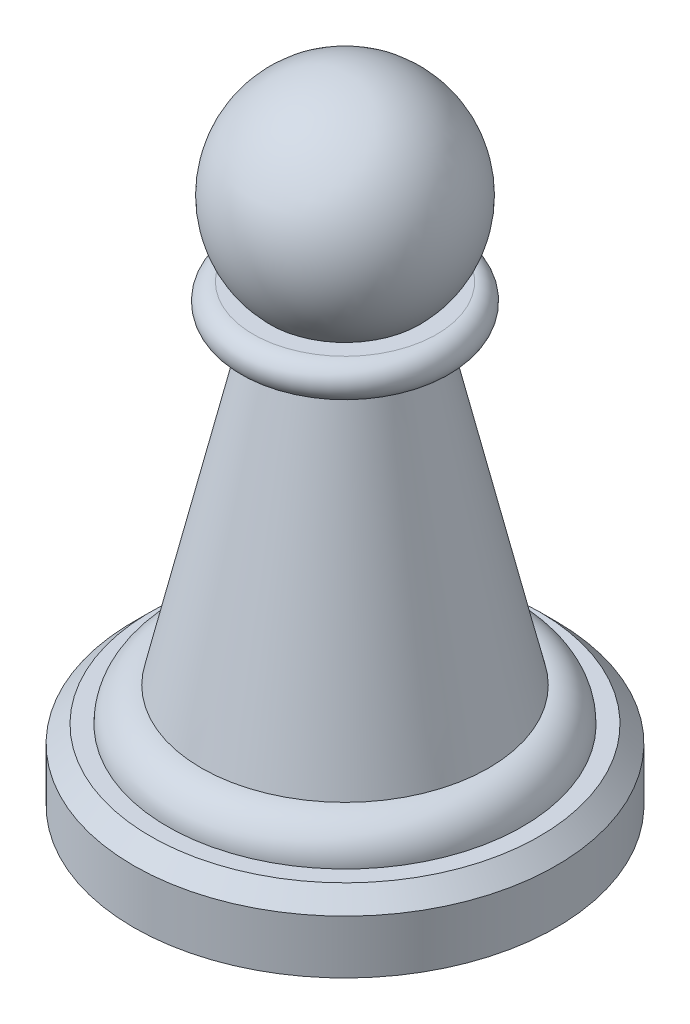
SolidWorks part; units mm, degrees
ref_plane "Front Plane" through (0, 0, 0) normal (0, 0, 1) x (1, 0, 0)
ref_plane "Top Plane" through (0, 0, 0) normal (0, 1, 0) x (1, 0, 0)
ref_plane "Right Plane" through (0, 0, 0) normal (1, 0, 0) x (0, 0, -1)
sketch "Sketch1" plane through (0, 0, 0) normal (0, 0, 1) x (1, 0, 0)
  line L0 (0, 0) -> (0, 28.575) construction
  line L1 (0, 0) -> (-9.525, 0)
  line L2 (-9.525, 0) -> (-9.525, 3.175)
  line L3 (-9.525, 3.175) -> (-8.001, 3.175)
  line L4 (-8.001, 3.175) -> (-8.001, 4.699)
  line L5 (-8.001, 4.699) -> (-6.477, 4.699)
  line L6 (-6.477, 4.699) -> (-3.175, 18.923)
  line L7 (-3.175, 18.923) -> (-4.1317, 18.923)
  line L9 (-4.1317, 20.447) -> (-3.3697, 20.447)
  line L10 (0, 28.575) -> (0, 0)
  arc A0 (0, 28.575) -> (-3.3697, 20.447) centre (0, 23.8125) ccw
  arc A1 (-4.1317, 18.923) -> (-4.1317, 20.447) centre (-4.1317, 19.685) cw
  dimension "D2" = 3.175
  dimension "D10" = 9.525
  dimension "D9" = 1.524
  dimension "D1" = 28.575
  dimension "D3" = 3.175
  dimension "D4" = 1.524
  dimension "D5" = 1.524
  dimension "D6" = 9.525
  dimension "D7" = 1.524
  dimension "D8" = 1.524
  dimension "D11" = 14.224
revolve "Revolve1" add sketch "Sketch1" angle 360 about L0
fillet "Fillet1" radius 1.524 1 edges at (0, 4.699, -8.001)
chamfer "Chamfer1" distance 0.762 angle 45 1 edges at (0, 3.175, -9.525)
